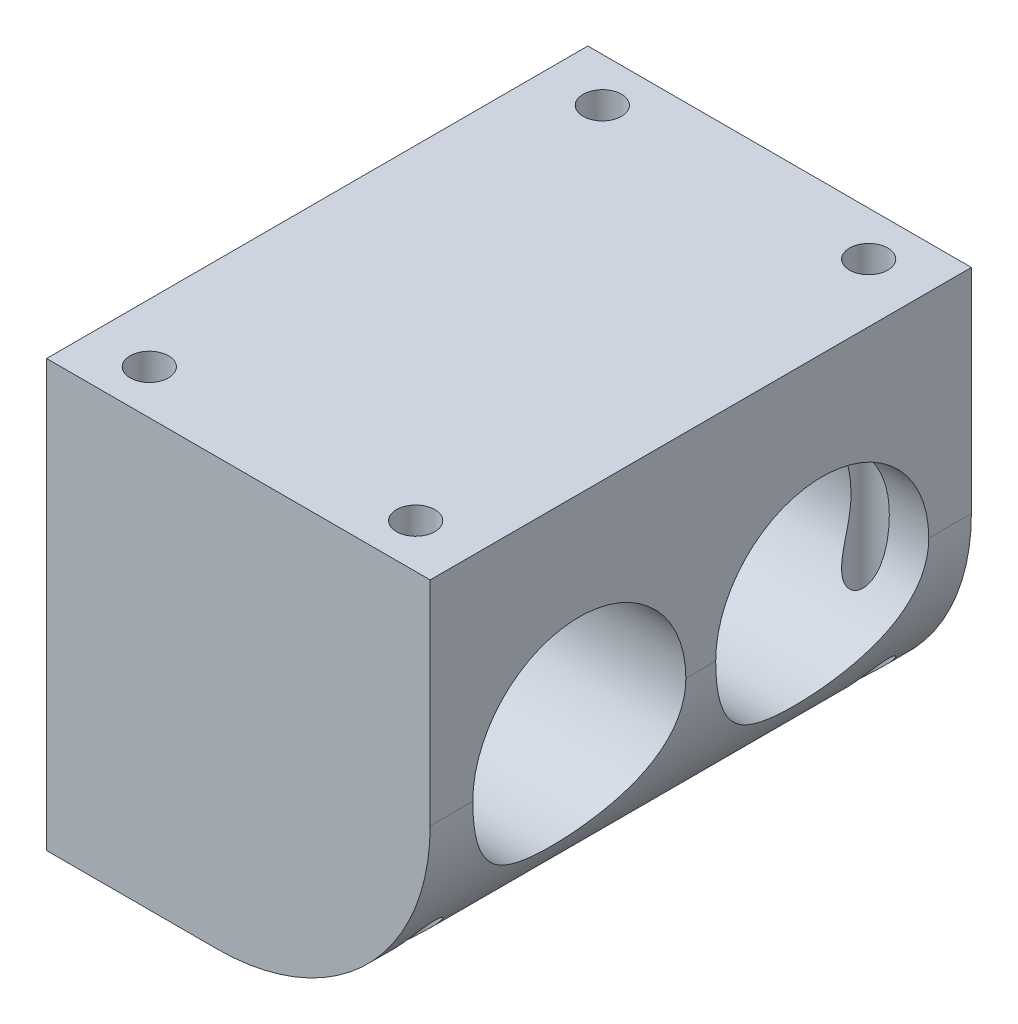
SolidWorks part; units mm, degrees
ref_plane "Front Plane" through (0, 0, 0) normal (0, 0, 1) x (1, 0, 0)
ref_plane "Top Plane" through (0, 0, 0) normal (0, 1, 0) x (1, 0, 0)
ref_plane "Right Plane" through (0, 0, 0) normal (1, 0, 0) x (0, 0, -1)
sketch "Sketch1" plane through (0, 0, 0) normal (0, 1, 0) x (1, 0, 0)
  line L1 (-9, 12.7) -> (9, 12.7)
  line L2 (-9, 12.7) -> (-9, -12.7)
  line L3 (-9, -12.7) -> (9, -12.7)
  line L4 (9, 12.7) -> (9, -12.7)
  line L5 (-9, 12.7) -> (9, -12.7) construction
  line L6 (-9, -12.7) -> (9, 12.7) construction
  line L7 (-6.25, 10.6299) -> (6.25, 10.6299) construction
  line L8 (-6.25, 10.6299) -> (-6.25, -10.6299) construction
  line L9 (-6.25, -10.6299) -> (6.25, -10.6299) construction
  line L10 (6.25, 10.6299) -> (6.25, -10.6299) construction
  line L11 (-6.25, 10.6299) -> (6.25, -10.6299) construction
  line L12 (-6.25, -10.6299) -> (6.25, 10.6299) construction
  circle A0 centre (-6.25, 10.6299) radius 0.9
  circle A1 centre (6.25, 10.6299) radius 0.9
  circle A2 centre (6.25, -10.6299) radius 0.9
  circle A3 centre (-6.25, -10.6299) radius 0.9
  point P0 (0, 0)
  point P6 (0, 0)
  dimension "D5" = 1.8
  dimension "D1" = 18
  dimension "D2" = 25.4
  dimension "D3" = 21.2598
  dimension "D4" = 12.5
extrude "Boss-Extrude1" add sketch "Sketch1" along normal blind 20
sketch "Sketch2" plane through (9, 0, 0) normal (1, 0, 0) x (0, 0, -1)
  line L0 (-12.7, 10) -> (12.7, 10) construction
  line L1 (-12.7, 20) -> (-12.7, 0) construction
  line L2 (12.7, 20) -> (12.7, 0) construction
  point P6 (-5.7, 10)
  point P7 (5.7, 10)
  dimension "D1" = 7
  dimension "D2" = 7
hole_wizard "CBORE for M5 SHCS1" positions "Sketch3" profile "Sketch4" counterbore size "M5" standard "ANSI Metric" end condition through all
sketch "Sketch3" plane through (9, 0, 0) normal (1, 0, 0) x (0, 0, -1)
  point P0 (-5.7, 10)
  point P3 (5.7, 10)
sketch "Sketch4" plane through (9, 10, 5.7) normal (0, 1, 0) x (0, 0, -1)
  line L0 (0, 0) -> (0, 18)
  line L1 (0, 18) -> (2.75, 18)
  line L3 (2.75, 18) -> (2.75, 12)
  line L4 (2.75, 12) -> (5, 12)
  line L5 (5, 12) -> (5, 0)
  line L7 (5, 0) -> (0, 0)
  line L11 (0, -6.35) -> (0, 107.95) construction
  dimension "Thru Hole Dia." = 5.5
  dimension "Thru Hole Depth" = 18
  dimension "C'Bore Dia." = 10
  dimension "C'Bore Depth" = 12
fillet "Fillet1" radius 10 1 edges at (9, 0, 0)
